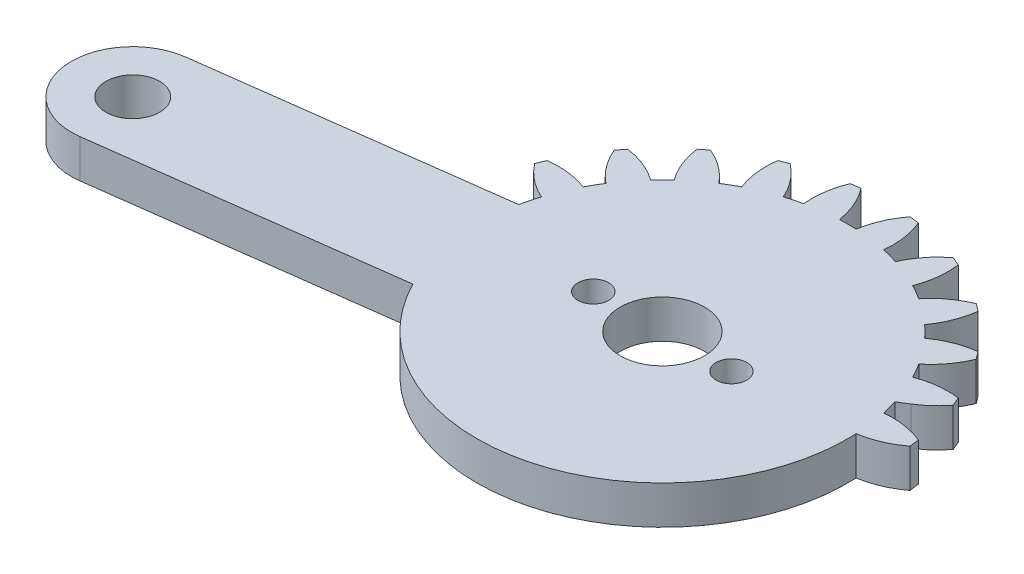
SolidWorks part; units mm, degrees
ref_plane "Front Plane" through (0, 0, 0) normal (0, 0, 1) x (1, 0, 0)
ref_plane "Top Plane" through (0, 0, 0) normal (0, 1, 0) x (1, 0, 0)
ref_plane "Right Plane" through (0, 0, 0) normal (1, 0, 0) x (0, 0, -1)
sketch "Sketch1" plane through (0, 0, 0) normal (0, 1, 0) x (1, 0, 0)
  line L0 (20.6437, 4) -> (2.0816, 4)
  line L1 (2.0816, -4) -> (20.6437, -4)
  arc A0 (2.0816, 4) -> (3.5217, 5.3071) centre (-0.7683, 8.5867) ccw
  arc A1 (3.5217, 5.3071) -> (3.2829, 5.8838) centre (-10.1063, 0) ccw
  arc A2 (3.2829, 5.8838) -> (0.6271, 5.5703) centre (2.5684, 0.5313) ccw
  arc A3 (0.6271, 5.5703) -> (0.0844, 6.5103) centre (-10.1063, 0) ccw
  arc A4 (0.0844, 6.5103) -> (1.6838, 8.6535) centre (-3.3089, 10.711) ccw
  arc A5 (1.6838, 8.6535) -> (1.3038, 9.1487) centre (-10.1063, 0) ccw
  arc A6 (1.3038, 9.1487) -> (-1.1803, 8.1585) centre (1.999, 3.7936) ccw
  arc A7 (-1.1803, 8.1585) -> (-1.9479, 8.926) centre (-10.1063, 0) ccw
  arc A8 (-1.9479, 8.926) -> (-0.9576, 11.4102) centre (-6.3127, 12.1053) ccw
  arc A9 (-0.9576, 11.4102) -> (-1.4528, 11.7901) centre (-10.1063, 0) ccw
  arc A10 (-1.4528, 11.7901) -> (-3.596, 10.1907) centre (0.6046, 6.7975) ccw
  arc A11 (-3.596, 10.1907) -> (-4.5361, 10.7334) centre (-10.1063, 0) ccw
  arc A12 (-4.5361, 10.7334) -> (-4.2225, 13.3892) centre (-9.5751, 12.6747) ccw
  arc A13 (-4.2225, 13.3892) -> (-4.7992, 13.6281) centre (-10.1063, 0) ccw
  arc A14 (-4.7992, 13.6281) -> (-6.4554, 11.5285) centre (-1.5196, 9.3381) ccw
  arc A15 (-6.4554, 11.5285) -> (-7.5039, 11.8094) centre (-10.1063, 0) ccw
  arc A16 (-7.5039, 11.8094) -> (-7.8884, 14.4558) centre (-12.8736, 12.3803) ccw
  arc A17 (-7.8884, 14.4558) -> (-8.5072, 14.5373) centre (-10.1063, 0) ccw
  arc A18 (-8.5072, 14.5373) -> (-9.5636, 12.0806) centre (-4.2291, 11.2423) ccw
  arc A19 (-9.5636, 12.0806) -> (-10.6491, 12.0806) centre (-10.1063, 0) ccw
  arc A20 (-10.6491, 12.0806) -> (-11.7054, 14.5373) centre (-15.9836, 11.2423) ccw
  arc A21 (-11.7054, 14.5373) -> (-12.3243, 14.4558) centre (-10.1063, 0) ccw
  arc A22 (-12.3243, 14.4558) -> (-12.7088, 11.8094) centre (-7.3391, 12.3803) ccw
  arc A23 (-12.7088, 11.8094) -> (-13.7573, 11.5285) centre (-10.1063, 0) ccw
  arc A24 (-13.7573, 11.5285) -> (-15.4135, 13.6281) centre (-18.6931, 9.3381) ccw
  arc A25 (-15.4135, 13.6281) -> (-15.9901, 13.3892) centre (-10.1063, 0) ccw
  arc A26 (-15.9901, 13.3892) -> (-15.6766, 10.7334) centre (-10.6376, 12.6747) ccw
  arc A27 (-15.6766, 10.7334) -> (-16.6166, 10.1907) centre (-10.1063, 0) ccw
  arc A28 (-16.6166, 10.1907) -> (-18.7599, 11.7901) centre (-20.8173, 6.7975) ccw
  arc A29 (-18.7599, 11.7901) -> (-19.255, 11.4102) centre (-10.1063, 0) ccw
  arc A30 (-19.255, 11.4102) -> (-18.2648, 8.926) centre (-13.9, 12.1053) ccw
  arc A31 (-18.2648, 8.926) -> (-19.0324, 8.1585) centre (-10.1063, 0) ccw
  arc A32 (-19.0324, 8.1585) -> (-21.5165, 9.1487) centre (-22.2117, 3.7936) ccw
  arc A33 (-21.5165, 9.1487) -> (-21.8965, 8.6535) centre (-10.1063, 0) ccw
  arc A34 (-21.8965, 8.6535) -> (-20.2971, 6.5103) centre (-16.9038, 10.711) ccw
  arc A35 (-20.2971, 6.5103) -> (-20.8398, 5.5703) centre (-10.1063, 0) ccw
  arc A36 (-20.8398, 5.5703) -> (-23.4956, 5.8838) centre (-22.7811, 0.5313) ccw
  arc A37 (-23.4956, 5.8838) -> (-23.7344, 5.3071) centre (-10.1063, 0) ccw
  arc A38 (-23.7344, 5.3071) -> (-21.6348, 3.6509) centre (-19.4444, 8.5867) ccw
  arc A39 (-21.6348, 3.6509) -> (-21.9157, 2.6025) centre (-10.1063, 0) ccw
  arc A40 (-21.9157, 2.6025) -> (-24.5622, 2.2179) centre (-22.4867, -2.7673) ccw
  arc A41 (-24.5622, 2.2179) -> (-24.6437, 1.5991) centre (-10.1063, 0) ccw
  arc A42 (-24.6437, 1.5991) -> (-22.1869, 0.5427) centre (-21.3486, 5.8773) ccw
  arc A43 (-22.1869, 0.5427) -> (-22.1869, -0.5427) centre (-10.1063, 0) ccw
  arc A44 (-22.1869, -0.5427) -> (-24.6437, -1.5991) centre (-21.3486, -5.8773) ccw
  arc A45 (-24.6437, -1.5991) -> (-24.5622, -2.2179) centre (-10.1063, 0) ccw
  arc A46 (-24.5622, -2.2179) -> (-21.9157, -2.6025) centre (-22.4867, 2.7673) ccw
  arc A47 (-21.9157, -2.6025) -> (-21.6348, -3.6509) centre (-10.1063, 0) ccw
  arc A48 (-21.6348, -3.6509) -> (-23.7344, -5.3071) centre (-19.4444, -8.5867) ccw
  arc A49 (-23.7344, -5.3071) -> (-23.4956, -5.8838) centre (-10.1063, 0) ccw
  arc A50 (-23.4956, -5.8838) -> (-20.8398, -5.5703) centre (-22.7811, -0.5313) ccw
  arc A51 (-20.8398, -5.5703) -> (-20.2971, -6.5103) centre (-10.1063, 0) ccw
  arc A52 (-20.2971, -6.5103) -> (-21.8965, -8.6535) centre (-16.9038, -10.711) ccw
  arc A53 (-21.8965, -8.6535) -> (-21.5165, -9.1487) centre (-10.1063, 0) ccw
  arc A54 (-21.5165, -9.1487) -> (-19.0324, -8.1585) centre (-22.2117, -3.7936) ccw
  arc A55 (-19.0324, -8.1585) -> (-18.2648, -8.926) centre (-10.1063, 0) ccw
  arc A56 (-18.2648, -8.926) -> (-19.255, -11.4102) centre (-13.9, -12.1053) ccw
  arc A57 (-19.255, -11.4102) -> (-18.7599, -11.7901) centre (-10.1063, 0) ccw
  arc A58 (-18.7599, -11.7901) -> (-16.6166, -10.1907) centre (-20.8173, -6.7975) ccw
  arc A59 (-16.6166, -10.1907) -> (-15.6766, -10.7334) centre (-10.1063, 0) ccw
  arc A60 (-15.6766, -10.7334) -> (-15.9901, -13.3892) centre (-10.6376, -12.6747) ccw
  arc A61 (-15.9901, -13.3892) -> (-15.4135, -13.6281) centre (-10.1063, 0) ccw
  arc A62 (-15.4135, -13.6281) -> (-13.7573, -11.5285) centre (-18.6931, -9.3381) ccw
  arc A63 (-13.7573, -11.5285) -> (-12.7088, -11.8094) centre (-10.1063, 0) ccw
  arc A64 (-12.7088, -11.8094) -> (-12.3243, -14.4558) centre (-7.3391, -12.3803) ccw
  arc A65 (-12.3243, -14.4558) -> (-11.7054, -14.5373) centre (-10.1063, 0) ccw
  arc A66 (-11.7054, -14.5373) -> (-10.6491, -12.0806) centre (-15.9836, -11.2423) ccw
  arc A67 (-10.6491, -12.0806) -> (-9.5636, -12.0806) centre (-10.1063, 0) ccw
  arc A68 (-9.5636, -12.0806) -> (-8.5072, -14.5373) centre (-4.2291, -11.2423) ccw
  arc A69 (-8.5072, -14.5373) -> (-7.8884, -14.4558) centre (-10.1063, 0) ccw
  arc A70 (-7.8884, -14.4558) -> (-7.5039, -11.8094) centre (-12.8736, -12.3803) ccw
  arc A71 (-7.5039, -11.8094) -> (-6.4554, -11.5285) centre (-10.1063, 0) ccw
  arc A72 (-6.4554, -11.5285) -> (-4.7992, -13.6281) centre (-1.5196, -9.3381) ccw
  arc A73 (-4.7992, -13.6281) -> (-4.2225, -13.3892) centre (-10.1063, 0) ccw
  arc A74 (-4.2225, -13.3892) -> (-4.5361, -10.7334) centre (-9.5751, -12.6747) ccw
  arc A75 (-4.5361, -10.7334) -> (-3.596, -10.1907) centre (-10.1063, 0) ccw
  arc A76 (-3.596, -10.1907) -> (-1.4528, -11.7901) centre (0.6046, -6.7975) ccw
  arc A77 (-1.4528, -11.7901) -> (-0.9576, -11.4102) centre (-10.1063, 0) ccw
  arc A78 (-0.9576, -11.4102) -> (-1.9479, -8.926) centre (-6.3127, -12.1053) ccw
  arc A79 (-1.9479, -8.926) -> (-1.1803, -8.1585) centre (-10.1063, 0) ccw
  arc A80 (-1.1803, -8.1585) -> (1.3038, -9.1487) centre (1.999, -3.7936) ccw
  arc A81 (1.3038, -9.1487) -> (1.6838, -8.6535) centre (-10.1063, 0) ccw
  arc A82 (1.6838, -8.6535) -> (0.0844, -6.5103) centre (-3.3089, -10.711) ccw
  arc A83 (0.0844, -6.5103) -> (0.6271, -5.5703) centre (-10.1063, 0) ccw
  arc A84 (0.6271, -5.5703) -> (3.2829, -5.8838) centre (2.5684, -0.5313) ccw
  arc A85 (3.2829, -5.8838) -> (3.5217, -5.3071) centre (-10.1063, 0) ccw
  arc A86 (3.5217, -5.3071) -> (2.0816, -4) centre (-0.7683, -8.5867) ccw
  arc A87 (20.6437, -4) -> (20.6437, 4) centre (20.6437, 0) ccw
  circle A88 centre (-10.1063, 0) radius 1.5
  circle A89 centre (20.6437, 0) radius 1.5
  dimension "D1" = 3
  dimension "D2" = 3
extrude "Boss-Extrude1" add sketch "Sketch1" along normal blind 2.5
sketch "Sketch3" plane through (0, 2.5, 0) normal (0, 1, 0) x (1, 0, 0)
  line L0 (-10.1063, 0) -> (-40.8563, 0) construction
  line L1 (-10.1063, 0) -> (-40.5933, -4.0137)
  line L2 (-10.6284, 3.9658) -> (-41.1154, -0.0479)
  line L3 (-9.5842, -3.9658) -> (-40.0712, -7.9795)
  line L4 (-10.1063, 0) -> (-4.5096, 13.5117) construction
  line L5 (-10.1063, 0) -> (-8.1974, 14.4999) construction
  circle A0 centre (-10.1063, 0) radius 1.5
  circle A1 centre (20.6437, 0) radius 1.5 construction
  circle A2 centre (20.6437, 0) radius 1.5
  circle A3 centre (-40.5933, -4.0137) radius 1.75
  circle A4 centre (-40.5933, -4.0137) radius 4
  circle A5 centre (-10.1063, 0) radius 4
  arc A6 (-4.2225, 13.3892) -> (-4.7992, 13.6281) centre (-10.1063, 0) ccw construction
  arc A7 (-7.8884, 14.4558) -> (-8.5072, 14.5373) centre (-10.1063, 0) ccw construction
  dimension "D2" = 3
  dimension "D5" = 3.5
  dimension "D6" = 8
  dimension "D7" = 8
  dimension "D1" = 30.75
  dimension "D4" = 7.5
extrude "Boss-Extrude2" add sketch "Sketch3" against normal blind 2.5 contours L0 A5 L2 | A5 L0 L2 A4 L1 | A4 A3 | A5 L1 A4 L3 | L0 A0 L1 A5 | A0 L0 A5 L1 region at (-13.19, 2.5, -2.3662) region at (-25.0786, 2.5, 4.0667) region at (-25.621, 2.5, -0.053) region at (-36.7147, 2.5, 3.7595)
sketch "Sketch4" plane through (0, 2.5, 0) normal (0, 1, 0) x (1, 0, 0)
  line L0 (20.6437, 4) -> (2.0816, 4) construction
  line L1 (2.0816, -4) -> (20.6437, -4) construction
  line L2 (20.6437, 4) -> (2.0816, 4)
  line L3 (2.0816, -4) -> (20.6437, -4)
  line L4 (2.0816, 4) -> (1.4381, 3.6001)
  line L5 (-21.6245, -5.5509) -> (-20.8986, -5.4553)
  line L6 (-10.1063, 0) -> (0.0844, 6.5103) construction
  line L7 (-10.1063, 0) -> (1.9742, 0.5427) construction
  line L8 (-24.5755, 2.1296) -> (-41.1154, -0.0479)
  line L9 (-40.0712, -7.9795) -> (-23.5312, -5.8019)
  line L10 (2.0816, -4) -> (20.6437, -4)
  line L11 (2.0816, -4) -> (20.6437, -4)
  line L12 (-21.9429, 2.4762) -> (-41.1154, -0.0479)
  line L13 (-40.0712, -7.9795) -> (-21.6245, -5.5509)
  line L18 (20.6437, 4) -> (2.0816, 4)
  line L19 (20.6437, 4) -> (2.0816, 4)
  circle A0 centre (-10.1063, 0) radius 12.0927
  arc A1 (3.2829, 5.8838) -> (0.6271, 5.5703) centre (2.5684, 0.5313) ccw construction
  arc A2 (3.5217, 5.3071) -> (3.2829, 5.8838) centre (-10.1063, 0) ccw construction
  arc A3 (2.0816, 4) -> (3.5217, 5.3071) centre (-0.7683, 8.5867) ccw construction
  arc A4 (20.6437, -4) -> (20.6437, 4) centre (20.6437, 0) ccw construction
  arc A5 (3.5217, -5.3071) -> (2.0816, -4) centre (-0.7683, -8.5867) ccw construction
  arc A6 (3.2829, -5.8838) -> (3.5217, -5.3071) centre (-10.1063, 0) ccw construction
  arc A7 (0.6271, -5.5703) -> (3.2829, -5.8838) centre (2.5684, -0.5313) ccw construction
  arc A8 (3.2829, 5.8838) -> (0.6271, 5.5703) centre (2.5684, 0.5313) ccw
  arc A9 (3.5217, 5.3071) -> (3.2829, 5.8838) centre (-10.1063, 0) ccw
  arc A10 (2.0816, 4) -> (3.5217, 5.3071) centre (-0.7683, 8.5867) ccw
  arc A11 (20.6437, -4) -> (20.6437, 4) centre (20.6437, 0) ccw
  arc A12 (3.5217, -5.3071) -> (2.0816, -4) centre (-0.7683, -8.5867) ccw
  arc A13 (3.2829, -5.8838) -> (3.5217, -5.3071) centre (-10.1063, 0) ccw
  arc A14 (0.6271, -5.5703) -> (3.2829, -5.8838) centre (2.5684, -0.5313) ccw
  arc A15 (1.9742, 0.5427) -> (4.431, 1.5991) centre (1.1359, 5.8773) ccw
  arc A16 (4.3495, 2.2179) -> (1.7031, 2.6025) centre (2.274, -2.7673) ccw
  arc A17 (4.431, 1.5991) -> (4.3495, 2.2179) centre (-10.1063, 0) ccw
  arc A64 (-20.2971, -6.5103) -> (-21.8965, -8.6535) centre (-16.9038, -10.711) ccw
  arc A65 (-20.2971, -6.5103) -> (-21.8965, -8.6535) centre (-16.9038, -10.711) ccw
  arc A66 (-21.8965, -8.6535) -> (-21.5165, -9.1487) centre (-10.1063, 0) ccw
  arc A67 (-21.8965, -8.6535) -> (-21.5165, -9.1487) centre (-10.1063, 0) ccw
  arc A68 (-21.5165, -9.1487) -> (-19.0324, -8.1585) centre (-22.2117, -3.7936) ccw
  arc A69 (-21.5165, -9.1487) -> (-19.0324, -8.1585) centre (-22.2117, -3.7936) ccw
  arc A70 (-18.2648, -8.926) -> (-19.255, -11.4102) centre (-13.9, -12.1053) ccw
  arc A71 (-18.2648, -8.926) -> (-19.255, -11.4102) centre (-13.9, -12.1053) ccw
  arc A95 (-21.6348, 3.6509) -> (-21.9157, 2.6025) centre (-10.1063, 0) ccw
  arc A96 (-41.1154, -0.0479) -> (-40.0712, -7.9795) centre (-40.5933, -4.0137) ccw
  arc A100 (-19.0324, -8.1585) -> (-18.2648, -8.926) centre (-10.1063, 0) ccw
  arc A111 (-19.255, -11.4102) -> (-18.7599, -11.7901) centre (-10.1063, 0) ccw
  arc A112 (-19.255, -11.4102) -> (-18.7599, -11.7901) centre (-10.1063, 0) ccw
  arc A113 (-18.7599, -11.7901) -> (-16.6166, -10.1907) centre (-20.8173, -6.7975) ccw
  arc A114 (-18.7599, -11.7901) -> (-16.6166, -10.1907) centre (-20.8173, -6.7975) ccw
  arc A115 (-16.6166, -10.1907) -> (-15.6766, -10.7334) centre (-10.1063, 0) ccw
  arc A116 (-16.6166, -10.1907) -> (-15.6766, -10.7334) centre (-10.1063, 0) ccw
  arc A117 (-15.6766, -10.7334) -> (-15.9901, -13.3892) centre (-10.6376, -12.6747) ccw
  arc A118 (-15.6766, -10.7334) -> (-15.9901, -13.3892) centre (-10.6376, -12.6747) ccw
  arc A119 (-15.9901, -13.3892) -> (-15.4135, -13.6281) centre (-10.1063, 0) ccw
  arc A120 (-15.9901, -13.3892) -> (-15.4135, -13.6281) centre (-10.1063, 0) ccw
  arc A121 (-15.4135, -13.6281) -> (-13.7573, -11.5285) centre (-18.6931, -9.3381) ccw
  arc A122 (-15.4135, -13.6281) -> (-13.7573, -11.5285) centre (-18.6931, -9.3381) ccw
  arc A123 (-13.7573, -11.5285) -> (-12.7088, -11.8094) centre (-10.1063, 0) ccw
  arc A124 (-13.7573, -11.5285) -> (-12.7088, -11.8094) centre (-10.1063, 0) ccw
  arc A125 (-12.7088, -11.8094) -> (-12.3243, -14.4558) centre (-7.3391, -12.3803) ccw
  arc A126 (-12.7088, -11.8094) -> (-12.3243, -14.4558) centre (-7.3391, -12.3803) ccw
  arc A127 (-12.3243, -14.4558) -> (-11.7054, -14.5373) centre (-10.1063, 0) ccw
  arc A128 (-12.3243, -14.4558) -> (-11.7054, -14.5373) centre (-10.1063, 0) ccw
  arc A129 (-11.7054, -14.5373) -> (-10.6491, -12.0806) centre (-15.9836, -11.2423) ccw
  arc A130 (-11.7054, -14.5373) -> (-10.6491, -12.0806) centre (-15.9836, -11.2423) ccw
  arc A131 (-10.6491, -12.0806) -> (-9.5636, -12.0806) centre (-10.1063, 0) ccw
  arc A132 (-10.6491, -12.0806) -> (-9.5636, -12.0806) centre (-10.1063, 0) ccw
  arc A133 (2.0816, 4) -> (3.5217, 5.3071) centre (-0.7683, 8.5867) ccw
  arc A134 (3.5217, 5.3071) -> (3.2829, 5.8838) centre (-10.1063, 0) ccw
  arc A135 (3.2829, 5.8838) -> (0.6271, 5.5703) centre (2.5684, 0.5313) ccw
  arc A136 (0.6271, 5.5703) -> (0.0844, 6.5103) centre (-10.1063, 0) ccw
  arc A137 (0.0844, 6.5103) -> (1.6838, 8.6535) centre (-3.3089, 10.711) ccw
  arc A138 (1.6838, 8.6535) -> (1.3038, 9.1487) centre (-10.1063, 0) ccw
  arc A139 (1.3038, 9.1487) -> (-1.1803, 8.1585) centre (1.999, 3.7936) ccw
  arc A140 (-1.1803, 8.1585) -> (-1.9479, 8.926) centre (-10.1063, 0) ccw
  arc A141 (-1.9479, 8.926) -> (-0.9576, 11.4102) centre (-6.3127, 12.1053) ccw
  arc A142 (-0.9576, 11.4102) -> (-1.4528, 11.7901) centre (-10.1063, 0) ccw
  arc A143 (-1.4528, 11.7901) -> (-3.596, 10.1907) centre (0.6046, 6.7975) ccw
  arc A144 (-3.596, 10.1907) -> (-4.5361, 10.7334) centre (-10.1063, 0) ccw
  arc A145 (-4.5361, 10.7334) -> (-4.2225, 13.3892) centre (-9.5751, 12.6747) ccw
  arc A146 (-4.2225, 13.3892) -> (-4.7992, 13.6281) centre (-10.1063, 0) ccw
  arc A147 (-4.7992, 13.6281) -> (-6.4554, 11.5285) centre (-1.5196, 9.3381) ccw
  arc A148 (-6.4554, 11.5285) -> (-7.5039, 11.8094) centre (-10.1063, 0) ccw
  arc A149 (-7.5039, 11.8094) -> (-7.8884, 14.4558) centre (-12.8736, 12.3803) ccw
  arc A150 (-7.8884, 14.4558) -> (-8.5072, 14.5373) centre (-10.1063, 0) ccw
  arc A151 (-8.5072, 14.5373) -> (-9.5636, 12.0806) centre (-4.2291, 11.2423) ccw
  arc A152 (-9.5636, 12.0806) -> (-10.6491, 12.0806) centre (-10.1063, 0) ccw
  arc A153 (-10.6491, 12.0806) -> (-11.7054, 14.5373) centre (-15.9836, 11.2423) ccw
  arc A154 (-11.7054, 14.5373) -> (-12.3243, 14.4558) centre (-10.1063, 0) ccw
  arc A155 (-12.3243, 14.4558) -> (-12.7088, 11.8094) centre (-7.3391, 12.3803) ccw
  arc A156 (-12.7088, 11.8094) -> (-13.7573, 11.5285) centre (-10.1063, 0) ccw
  arc A157 (-13.7573, 11.5285) -> (-15.4135, 13.6281) centre (-18.6931, 9.3381) ccw
  arc A158 (-15.4135, 13.6281) -> (-15.9901, 13.3892) centre (-10.1063, 0) ccw
  arc A159 (-15.9901, 13.3892) -> (-15.6766, 10.7334) centre (-10.6376, 12.6747) ccw
  arc A160 (-15.6766, 10.7334) -> (-16.6166, 10.1907) centre (-10.1063, 0) ccw
  arc A161 (-16.6166, 10.1907) -> (-18.7599, 11.7901) centre (-20.8173, 6.7975) ccw
  arc A162 (-18.7599, 11.7901) -> (-19.255, 11.4102) centre (-10.1063, 0) ccw
  arc A163 (-19.255, 11.4102) -> (-18.2648, 8.926) centre (-13.9, 12.1053) ccw
  arc A164 (-18.2648, 8.926) -> (-19.0324, 8.1585) centre (-10.1063, 0) ccw
  arc A165 (-19.0324, 8.1585) -> (-21.5165, 9.1487) centre (-22.2117, 3.7936) ccw
  arc A166 (-21.5165, 9.1487) -> (-21.8965, 8.6535) centre (-10.1063, 0) ccw
  arc A167 (-21.8965, 8.6535) -> (-20.2971, 6.5103) centre (-16.9038, 10.711) ccw
  arc A168 (-20.2971, 6.5103) -> (-20.8398, 5.5703) centre (-10.1063, 0) ccw
  arc A169 (-20.8398, 5.5703) -> (-23.4956, 5.8838) centre (-22.7811, 0.5313) ccw
  arc A170 (-23.4956, 5.8838) -> (-23.7344, 5.3071) centre (-10.1063, 0) ccw
  arc A171 (-23.7344, 5.3071) -> (-21.6348, 3.6509) centre (-19.4444, 8.5867) ccw
  arc A172 (-21.6348, 3.6509) -> (-21.9157, 2.6025) centre (-10.1063, 0) ccw
  arc A173 (-9.5636, -12.0806) -> (-8.5072, -14.5373) centre (-4.2291, -11.2423) ccw
  arc A174 (-9.5636, -12.0806) -> (-8.5072, -14.5373) centre (-4.2291, -11.2423) ccw
  arc A175 (-8.5072, -14.5373) -> (-7.8884, -14.4558) centre (-10.1063, 0) ccw
  arc A176 (-41.1154, -0.0479) -> (-40.0712, -7.9795) centre (-40.5933, -4.0137) ccw
  arc A177 (-8.5072, -14.5373) -> (-7.8884, -14.4558) centre (-10.1063, 0) ccw
  arc A178 (-7.8884, -14.4558) -> (-7.5039, -11.8094) centre (-12.8736, -12.3803) ccw
  arc A179 (-7.8884, -14.4558) -> (-7.5039, -11.8094) centre (-12.8736, -12.3803) ccw
  arc A180 (-19.0324, -8.1585) -> (-18.2648, -8.926) centre (-10.1063, 0) ccw
  arc A181 (-7.5039, -11.8094) -> (-6.4554, -11.5285) centre (-10.1063, 0) ccw
  arc A182 (-7.5039, -11.8094) -> (-6.4554, -11.5285) centre (-10.1063, 0) ccw
  arc A183 (-6.4554, -11.5285) -> (-4.7992, -13.6281) centre (-1.5196, -9.3381) ccw
  arc A184 (-6.4554, -11.5285) -> (-4.7992, -13.6281) centre (-1.5196, -9.3381) ccw
  arc A185 (-4.7992, -13.6281) -> (-4.2225, -13.3892) centre (-10.1063, 0) ccw
  arc A186 (-4.7992, -13.6281) -> (-4.2225, -13.3892) centre (-10.1063, 0) ccw
  arc A187 (-4.2225, -13.3892) -> (-4.5361, -10.7334) centre (-9.5751, -12.6747) ccw
  arc A188 (-4.2225, -13.3892) -> (-4.5361, -10.7334) centre (-9.5751, -12.6747) ccw
  arc A189 (-4.5361, -10.7334) -> (-3.596, -10.1907) centre (-10.1063, 0) ccw
  arc A190 (-4.5361, -10.7334) -> (-3.596, -10.1907) centre (-10.1063, 0) ccw
  arc A191 (-3.596, -10.1907) -> (-1.4528, -11.7901) centre (0.6046, -6.7975) ccw
  arc A192 (-3.596, -10.1907) -> (-1.4528, -11.7901) centre (0.6046, -6.7975) ccw
  arc A193 (-1.4528, -11.7901) -> (-0.9576, -11.4102) centre (-10.1063, 0) ccw
  arc A194 (-1.4528, -11.7901) -> (-0.9576, -11.4102) centre (-10.1063, 0) ccw
  arc A195 (-0.9576, -11.4102) -> (-1.9479, -8.926) centre (-6.3127, -12.1053) ccw
  arc A196 (-0.9576, -11.4102) -> (-1.9479, -8.926) centre (-6.3127, -12.1053) ccw
  arc A197 (-1.9479, -8.926) -> (-1.1803, -8.1585) centre (-10.1063, 0) ccw
  arc A198 (-1.9479, -8.926) -> (-1.1803, -8.1585) centre (-10.1063, 0) ccw
  arc A199 (-1.1803, -8.1585) -> (1.3038, -9.1487) centre (1.999, -3.7936) ccw
  arc A200 (-1.1803, -8.1585) -> (1.3038, -9.1487) centre (1.999, -3.7936) ccw
  arc A201 (1.3038, -9.1487) -> (1.6838, -8.6535) centre (-10.1063, 0) ccw
  arc A202 (1.3038, -9.1487) -> (1.6838, -8.6535) centre (-10.1063, 0) ccw
  arc A203 (1.6838, -8.6535) -> (0.0844, -6.5103) centre (-3.3089, -10.711) ccw
  arc A204 (1.6838, -8.6535) -> (0.0844, -6.5103) centre (-3.3089, -10.711) ccw
  arc A205 (0.0844, -6.5103) -> (0.6271, -5.5703) centre (-10.1063, 0) ccw
  arc A206 (0.0844, -6.5103) -> (0.6271, -5.5703) centre (-10.1063, 0) ccw
  arc A207 (0.6271, -5.5703) -> (3.2829, -5.8838) centre (2.5684, -0.5313) ccw
  arc A208 (0.6271, -5.5703) -> (3.2829, -5.8838) centre (2.5684, -0.5313) ccw
  arc A209 (3.2829, -5.8838) -> (3.5217, -5.3071) centre (-10.1063, 0) ccw
  arc A210 (3.2829, -5.8838) -> (3.5217, -5.3071) centre (-10.1063, 0) ccw
  arc A211 (3.5217, -5.3071) -> (2.0816, -4) centre (-0.7683, -8.5867) ccw
  arc A212 (3.5217, -5.3071) -> (2.0816, -4) centre (-0.7683, -8.5867) ccw
  arc A213 (2.0816, 4) -> (3.5217, 5.3071) centre (-0.7683, 8.5867) ccw
  arc A214 (3.5217, 5.3071) -> (3.2829, 5.8838) centre (-10.1063, 0) ccw
  arc A215 (3.2829, 5.8838) -> (0.6271, 5.5703) centre (2.5684, 0.5313) ccw
  arc A216 (0.6271, 5.5703) -> (0.0844, 6.5103) centre (-10.1063, 0) ccw
  arc A217 (0.0844, 6.5103) -> (1.6838, 8.6535) centre (-3.3089, 10.711) ccw
  arc A218 (1.6838, 8.6535) -> (1.3038, 9.1487) centre (-10.1063, 0) ccw
  arc A219 (1.3038, 9.1487) -> (-1.1803, 8.1585) centre (1.999, 3.7936) ccw
  arc A220 (-1.1803, 8.1585) -> (-1.9479, 8.926) centre (-10.1063, 0) ccw
  arc A221 (-1.9479, 8.926) -> (-0.9576, 11.4102) centre (-6.3127, 12.1053) ccw
  arc A222 (-0.9576, 11.4102) -> (-1.4528, 11.7901) centre (-10.1063, 0) ccw
  arc A223 (-1.4528, 11.7901) -> (-3.596, 10.1907) centre (0.6046, 6.7975) ccw
  arc A224 (-3.596, 10.1907) -> (-4.5361, 10.7334) centre (-10.1063, 0) ccw
  arc A225 (-4.5361, 10.7334) -> (-4.2225, 13.3892) centre (-9.5751, 12.6747) ccw
  arc A226 (-4.2225, 13.3892) -> (-4.7992, 13.6281) centre (-10.1063, 0) ccw
  arc A227 (-4.7992, 13.6281) -> (-6.4554, 11.5285) centre (-1.5196, 9.3381) ccw
  arc A228 (-6.4554, 11.5285) -> (-7.5039, 11.8094) centre (-10.1063, 0) ccw
  arc A229 (-7.5039, 11.8094) -> (-7.8884, 14.4558) centre (-12.8736, 12.3803) ccw
  arc A230 (-7.8884, 14.4558) -> (-8.5072, 14.5373) centre (-10.1063, 0) ccw
  arc A231 (-8.5072, 14.5373) -> (-9.5636, 12.0806) centre (-4.2291, 11.2423) ccw
  arc A232 (-9.5636, 12.0806) -> (-10.6491, 12.0806) centre (-10.1063, 0) ccw
  arc A233 (-10.6491, 12.0806) -> (-11.7054, 14.5373) centre (-15.9836, 11.2423) ccw
  arc A234 (-11.7054, 14.5373) -> (-12.3243, 14.4558) centre (-10.1063, 0) ccw
  arc A235 (-12.3243, 14.4558) -> (-12.7088, 11.8094) centre (-7.3391, 12.3803) ccw
  arc A236 (-12.7088, 11.8094) -> (-13.7573, 11.5285) centre (-10.1063, 0) ccw
  arc A237 (-13.7573, 11.5285) -> (-15.4135, 13.6281) centre (-18.6931, 9.3381) ccw
  arc A238 (-15.4135, 13.6281) -> (-15.9901, 13.3892) centre (-10.1063, 0) ccw
  arc A239 (-15.9901, 13.3892) -> (-15.6766, 10.7334) centre (-10.6376, 12.6747) ccw
  arc A240 (-15.6766, 10.7334) -> (-16.6166, 10.1907) centre (-10.1063, 0) ccw
  arc A241 (-16.6166, 10.1907) -> (-18.7599, 11.7901) centre (-20.8173, 6.7975) ccw
  arc A242 (-18.7599, 11.7901) -> (-19.255, 11.4102) centre (-10.1063, 0) ccw
  arc A243 (-19.255, 11.4102) -> (-18.2648, 8.926) centre (-13.9, 12.1053) ccw
  arc A244 (-18.2648, 8.926) -> (-19.0324, 8.1585) centre (-10.1063, 0) ccw
  arc A245 (-19.0324, 8.1585) -> (-21.5165, 9.1487) centre (-22.2117, 3.7936) ccw
  arc A246 (-21.5165, 9.1487) -> (-21.8965, 8.6535) centre (-10.1063, 0) ccw
  arc A247 (-21.8965, 8.6535) -> (-20.2971, 6.5103) centre (-16.9038, 10.711) ccw
  arc A248 (-20.2971, 6.5103) -> (-20.8398, 5.5703) centre (-10.1063, 0) ccw
  arc A249 (-20.8398, 5.5703) -> (-23.4956, 5.8838) centre (-22.7811, 0.5313) ccw
  arc A250 (-23.4956, 5.8838) -> (-23.7344, 5.3071) centre (-10.1063, 0) ccw
  arc A251 (-23.7344, 5.3071) -> (-21.6348, 3.6509) centre (-19.4444, 8.5867) ccw
  arc A252 (20.6437, -4) -> (20.6437, 4) centre (20.6437, 0) ccw
  arc A253 (20.6437, -4) -> (20.6437, 4) centre (20.6437, 0) ccw
  arc A254 (-21.9157, 2.6025) -> (-24.5622, 2.2179) centre (-22.4867, -2.7673) ccw
  arc A255 (-21.9157, 2.6025) -> (-24.5622, 2.2179) centre (-22.4867, -2.7673) ccw
  arc A256 (-24.5622, 2.2179) -> (-24.5755, 2.1296) centre (-10.1063, 0) ccw
  arc A257 (-24.5622, 2.2179) -> (-24.5755, 2.1296) centre (-10.1063, 0) ccw
  arc A258 (-23.5312, -5.8019) -> (-23.4956, -5.8838) centre (-10.1063, 0) ccw
  arc A259 (-23.5312, -5.8019) -> (-23.4956, -5.8838) centre (-10.1063, 0) ccw
  arc A260 (-23.4956, -5.8838) -> (-20.8398, -5.5703) centre (-22.7811, -0.5313) ccw
  arc A261 (-23.4956, -5.8838) -> (-20.8398, -5.5703) centre (-22.7811, -0.5313) ccw
  arc A262 (-20.8398, -5.5703) -> (-20.2971, -6.5103) centre (-10.1063, 0) ccw
  arc A263 (-20.8398, -5.5703) -> (-20.2971, -6.5103) centre (-10.1063, 0) ccw
  point P40 (-10.1063, 0)
  dimension "D2" = 24.1855
  dimension "D4" = 30
  dimension "D1" = 0
  dimension "D3" = 2
extrude "Cut-Extrude1" cut sketch "Sketch4" against normal blind 4 contours A67 A69 A0 L5 A65 | A112 A114 A0 A71 | A120 A122 A0 A118 | A128 A130 A0 A126 | A177 A179 A0 A174 | A186 A188 A0 A184 | A194 A196 A0 A192 | A202 A204 A0 A200 | A255 A257 L12 A0 | L13 A259 A261 A0 L5 | A0 A14 A13 A12 L3 A11 L2 L4 region at (12.7894, 2.5, 0.1545) region at (0.3325, 2.5, 8.01) region at (-2.0963, 2.5, 10.4389) region at (-5.071, 2.5, 12.1563) region at (-8.3889, 2.5, 13.0454) region at (-11.8238, 2.5, 13.0454) region at (-15.1417, 2.5, 12.1563) region at (-18.1164, 2.5, 10.4389) region at (-20.5452, 2.5, 8.01) region at (-23.2126, 2.5, -2.4243) region at (-22.1386, 2.5, 5.7339)
sketch "Sketch5" plane through (0, 2.5, 0) normal (0, 1, 0) x (1, 0, 0)
  circle A0 centre (-10.1063, 0) radius 2.75
  circle A1 centre (-5.6063, 0) radius 1
  circle A2 centre (-14.6063, 0) radius 1
  circle A3 centre (-10.1063, 0) radius 1.5 construction
  dimension "D1" = 5.5
  dimension "D2" = 2
  dimension "D3" = 2
  dimension "D4" = 4.5
  dimension "D5" = 9
extrude "Cut-Extrude2" cut sketch "Sketch5" against normal up to next contours A2 | A1 | A0 region at (-5.6063, 2.5, 0) region at (-14.6063, 2.5, 0)
